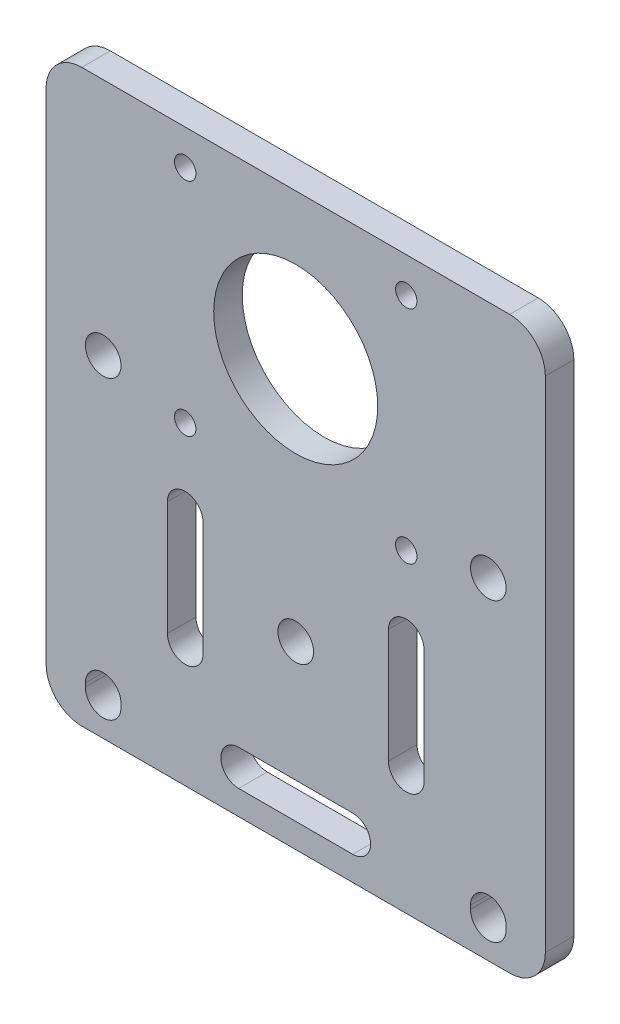
SolidWorks part; units mm, degrees
ref_plane "Front" through (0, 0, 0) normal (0, 0, 1) x (1, 0, 0)
ref_plane "Top" through (0, 0, 0) normal (0, 1, 0) x (1, 0, 0)
ref_plane "Right" through (0, 0, 0) normal (1, 0, 0) x (0, 0, -1)
sketch "Sketch4" plane through (0, 0, 0) normal (0, 0, 1) x (1, 0, 0)
  line L0 (-27, -34.5) -> (-27, -35) construction
  line L1 (-35, 40) -> (35, 40)
  line L2 (-35, 40) -> (-35, -40)
  line L3 (-35, -40) -> (35, -40)
  line L4 (35, 40) -> (35, -40)
  line L5 (-35, 40) -> (35, -40) construction
  line L6 (-35, -40) -> (35, 40) construction
  line L7 (-24.5, -34.5) -> (-24.5, -35)
  line L8 (-29.5, -34.5) -> (-29.5, -35)
  line L9 (0, -47.1607) -> (0, 39.6245) construction
  line L10 (27, -34.5) -> (27, -35) construction
  line L11 (24.5, -34.5) -> (24.5, -35)
  line L12 (29.5, -34.5) -> (29.5, -35)
  circle A0 centre (-27, 6.5) radius 2.5
  arc A1 (-24.5, -34.5) -> (-29.5, -34.5) centre (-27, -34.5) ccw
  arc A2 (-29.5, -35) -> (-24.5, -35) centre (-27, -35) ccw
  arc A3 (24.5, -34.5) -> (29.5, -34.5) centre (27, -34.5) cw
  arc A4 (29.5, -35) -> (24.5, -35) centre (27, -35) cw
  circle A5 centre (27, 6.5) radius 2.5
  point P0 (0, 0)
  point P10 (-27, -34.75)
  point P19 (27, -34.75)
  dimension "D3" = 27
  dimension "D6" = 2.5
  dimension "D1" = 70
  dimension "D2" = 80
  dimension "D4" = 41
  dimension "D5" = 0.5
  dimension "D7" = 5
extrude "Boss-Extrude2" add sketch "Sketch4" along normal blind 4
sketch "Sketch5" plane through (0, 0, 4) normal (0, 0, 1) x (1, 0, 0)
  line L0 (0, 46.583) -> (0, -17.262) construction
  line L1 (-44.8343, 19.5767) -> (52.8956, 19.5767) construction
  line L2 (-26.4123, 4.5701) -> (26.4123, -34.0701) construction
  line L3 (-27, -34.5) -> (27, 5) construction
  line L4 (-8, -34.0701) -> (8, -34.0701) construction
  line L5 (-8, -31.5701) -> (8, -31.5701)
  line L6 (-8, -36.5701) -> (8, -36.5701)
  line L7 (-15.5, -6.75) -> (-15.5, -22.75) construction
  line L8 (-13, -6.75) -> (-13, -22.75)
  line L9 (-18, -6.75) -> (-18, -22.75)
  line L10 (0, -5.3618) -> (0, -23.281) construction
  line L11 (15.5, -6.75) -> (15.5, -22.75) construction
  line L12 (13, -6.75) -> (13, -22.75)
  line L13 (18, -6.75) -> (18, -22.75)
  circle A0 centre (0, 19.5767) radius 11.5
  circle A1 centre (27, 6.5) radius 2.5 construction
  circle A2 centre (-15.5, 35.0767) radius 1.5
  circle A9 centre (15.5, 35.0767) radius 1.5
  circle A10 centre (15.5, 4.0767) radius 1.5
  circle A11 centre (-15.5, 4.0767) radius 1.5
  circle A12 centre (0, -14.75) radius 2.5
  arc A13 (-8, -31.5701) -> (-8, -36.5701) centre (-8, -34.0701) ccw
  arc A14 (8, -36.5701) -> (8, -31.5701) centre (8, -34.0701) ccw
  arc A15 (-13, -6.75) -> (-18, -6.75) centre (-15.5, -6.75) ccw
  arc A16 (-18, -22.75) -> (-13, -22.75) centre (-15.5, -22.75) ccw
  arc A17 (13, -6.75) -> (18, -6.75) centre (15.5, -6.75) cw
  arc A18 (18, -22.75) -> (13, -22.75) centre (15.5, -22.75) cw
  point P26 (0, -34.0701)
  point P33 (-15.5, -14.75)
  point P42 (15.5, -14.75)
  dimension "D1" = 23
  dimension "D3" = 3
  dimension "D6" = 16
  dimension "D7" = 2.5
  dimension "D9" = 2.5
  dimension "D10" = 5
  dimension "D2" = 30
  dimension "D4" = 15.5
  dimension "D5" = 15.5
  dimension "D8" = 16
extrude "Cut-Extrude2" cut sketch "Sketch5" against normal through all
fillet "Fillet1" radius 5 4 edges at (-35, -40, 2) (35, -40, 2) (35, 40, 2) (-35, 40, 2)
